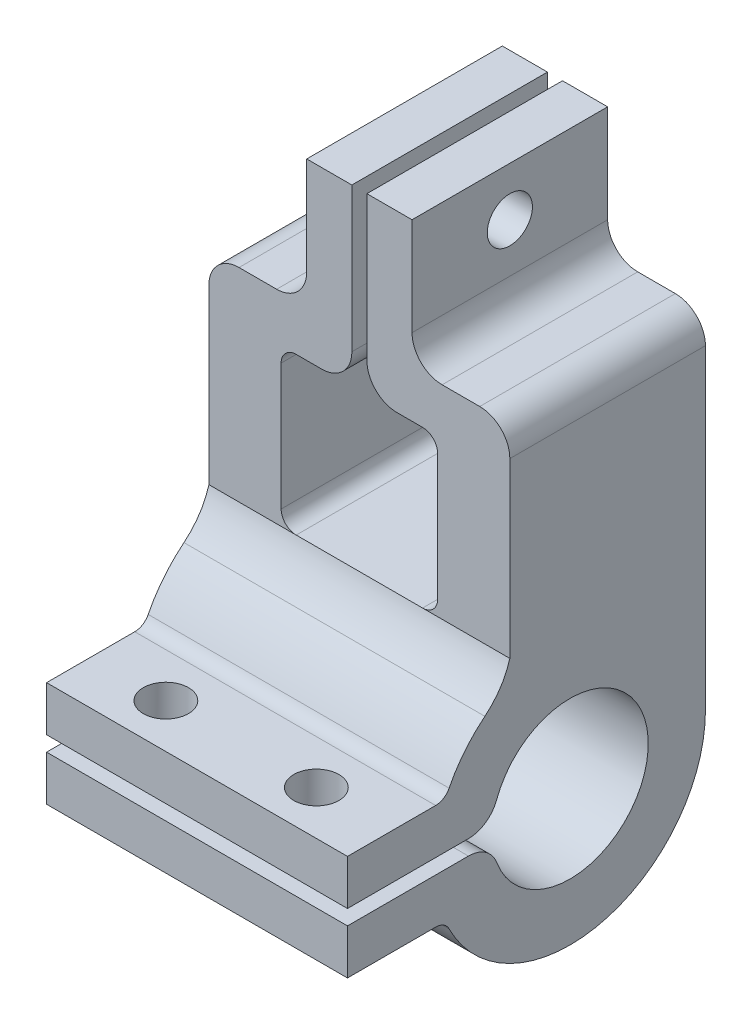
SolidWorks part; units mm, degrees
material "ABS"
ref_plane "Front Plane" through (0, 0, 0) normal (0, 0, 1) x (1, 0, 0)
ref_plane "Top Plane" through (0, 0, 0) normal (0, 1, 0) x (1, 0, 0)
ref_plane "Right Plane" through (0, 0, 0) normal (1, 0, 0) x (0, 0, -1)
sketch "Sketch1" plane through (0, 0, 0) normal (1, 0, 0) x (0, 0, -1)
  line L0 (0, 0) -> (0, 9) construction
  line L1 (0, 0) -> (-21.5165, 0) construction
  line L3 (-5.1759, 0.5) -> (-14.7916, 0.5)
  line L4 (-14.7916, 0.5) -> (-14.7916, 3.5)
  line L5 (-14.7916, 3.5) -> (-8.2916, 3.5)
  line L6 (-14.7916, -3.5) -> (-8.2916, -3.5)
  line L7 (-14.7916, -0.5) -> (-14.7916, -3.5)
  line L8 (-5.1759, -0.5) -> (-14.7916, -0.5)
  circle A0 centre (0, 0) radius 5.2 construction
  circle A1 centre (0, 0) radius 9 construction
  arc A2 (-8.2916, 3.5) -> (-8.2916, -3.5) centre (0, 0) cw
  arc A3 (-5.1759, 0.5) -> (-5.1759, -0.5) centre (0, 0) cw
  dimension "D1" = 10.4
  dimension "D2" = 18
  dimension "D4" = 0.5
  dimension "D5" = 3
  dimension "D6" = 6.5
extrude "Boss-Extrude1" add sketch "Sketch1" along normal blind 10 and the other way blind 10
fillet "Fillet1" radius 1 2 edges at (0, -3.5, 8.2916) (0, 3.5, 8.2916)
sketch "Sketch2" plane through (0, 0, 0) normal (1, 0, 0) x (0, 0, -1)
  line L0 (0, 0) -> (0, 9) construction
  line L1 (-4, 8.0623) -> (-4, 9.5)
  line L2 (-4, 9.5) -> (4, 9.5)
  line L3 (4, 9.5) -> (4, 8.0623) construction
  line L4 (-4, 8.0623) -> (4, 8.0623)
  line L5 (4, 9.5) -> (9, 9.5)
  line L6 (9, 9.5) -> (9, 0)
  arc A0 (-8.0373, -4.05) -> (-8.0373, 4.05) centre (0, 0) ccw construction
  arc A1 (-8.0373, -4.05) -> (-8.0373, 4.05) centre (0, 0) ccw construction
  arc A2 (9, 0) -> (4, 8.0623) centre (0, 0) ccw
  point P7 (0, 9.5)
  dimension "D1" = 8
  dimension "D2" = 0.5
extrude "Boss-Extrude2" add sketch "Sketch2" along normal up to surface (10 mm away) and the other way up to surface (10 mm away) up to face at (10, 0, 7.5884) other way up to face at (-10, 0, 7.5884)
fillet "Fillet2" radius 5 1 edges at (0, 8.0623, 4)
sketch "Sketch3" plane through (0, 0, 0) normal (0, 0, 1) x (1, 0, 0)
  line L0 (0, 0) -> (0, 19.9) construction
  line L3 (-5.2, 9.5) -> (-5.2, 19.9)
  line L4 (-5.2, 19.9) -> (5.2, 19.9) construction
  line L5 (5.2, 19.9) -> (5.2, 9.5)
  line L12 (0.5, 19.9) -> (0.5, 31.5)
  line L13 (0.5, 31.5) -> (3.5, 31.5)
  line L14 (3.5, 31.5) -> (3.5, 23)
  line L15 (-3.5, 31.5) -> (-3.5, 23)
  line L16 (-0.5, 31.5) -> (-3.5, 31.5)
  line L17 (-0.5, 19.9) -> (-0.5, 31.5)
  line L18 (-5.2, 19.9) -> (-0.5, 19.9)
  line L19 (0.5, 19.9) -> (5.2, 19.9)
  line L23 (10, 6.9975) -> (10, 9.5) construction
  line L24 (10, 9.5) -> (10, 23)
  line L27 (-10, 9.5) -> (-10, 6.9975) construction
  line L28 (-10, 9.5) -> (-10, 23)
  line L30 (-10, 23) -> (-3.5, 23)
  line L31 (3.5, 23) -> (10, 23)
  line L32 (-10, 9.5) -> (-5.2, 9.5)
  line L33 (5.2, 9.5) -> (10, 9.5)
  point P9 (0, 19.9)
  dimension "D1" = 9.5
  dimension "D2" = 10.4
  dimension "D3" = 10.4
  dimension "D4" = 0.5
  dimension "D5" = 3
  dimension "D6" = 8.5
  dimension "D7" = 13.5
extrude "Boss-Extrude3" add sketch "Sketch3" along normal up to vertex (4 mm away) and the other way up to surface (9 mm away) up to point (10, 9.5, 4) other way up to face at (0, 4.75, -9)
fillet "Fillet3" radius 1 4 edges at (-5.2, 19.9, -2.5) (5.2, 19.9, -2.5) (5.2, 9.5, -2.5) (-5.2, 9.5, -2.5)
fillet "Fillet4" radius 2 4 edges at (10, 23, -2.5) (3.5, 23, -2.5) (-3.5, 23, -2.5) (-10, 23, -2.5)
sketch "Sketch4" plane through (0, 3.5, 0) normal (0, 1, 0) x (1, 0, 0)
  line L0 (0, -14.7916) -> (0, -8.9303) construction
  line L1 (0, -11.8609) -> (10, -11.8609) construction
  line L2 (0, -11.8609) -> (-10, -11.8609) construction
  line L4 (10, -14.7916) -> (10, -8.9303)
  line L5 (10, -8.9303) -> (-10, -8.9303)
  line L6 (-10, -8.9303) -> (-10, -14.7916)
  line L7 (-10, -14.7916) -> (10, -14.7916)
  line L8 (10, -14.7916) -> (10, -8.9303) construction
  line L9 (10, -8.9303) -> (-10, -8.9303) construction
  line L10 (-10, -8.9303) -> (-10, -14.7916) construction
  line L11 (-10, -14.7916) -> (10, -14.7916) construction
  circle A0 centre (-5, -11.8609) radius 1.5
  circle A1 centre (5, -11.8609) radius 1.5
  dimension "D2" = 3
  dimension "D1" = 0
extrude "Cut-Extrude1" cut sketch "Sketch4" against normal up to surface (7 mm away) up to face at (0, -3.5, 11.8609)
sketch "Sketch5" plane through (0, 0, 0) normal (1, 0, 0) x (0, 0, -1)
  line L4 (-4, 31.5) -> (-4, 25)
  line L5 (-4, 25) -> (9, 25)
  line L6 (9, 25) -> (9, 31.5)
  line L7 (9, 31.5) -> (-4, 31.5)
  line L8 (-4, 31.5) -> (-4, 25) construction
  line L10 (9, 25) -> (9, 31.5) construction
  line L11 (9, 31.5) -> (-4, 31.5) construction
  line L12 (-4, 25) -> (9, 25)
  circle A0 centre (2.5, 28.25) radius 1.5
  point P7 (9, 28.25)
  point P8 (2.5, 31.5)
  dimension "D2" = 3
  dimension "D1" = 0
extrude "Cut-Extrude2" cut sketch "Sketch5" against normal up to surface and the other way up to surface contours A0 up to face at (-3.5, 28.25, -2.5) other way up to face at (3.5, 28.25, -2.5)
fillet "Fillet5" radius 2 4 edges at (0, 0.5, 5.1759) (0, -0.5, 5.1759) (0.5, 19.9, -2.5) (-0.5, 19.9, -2.5)
